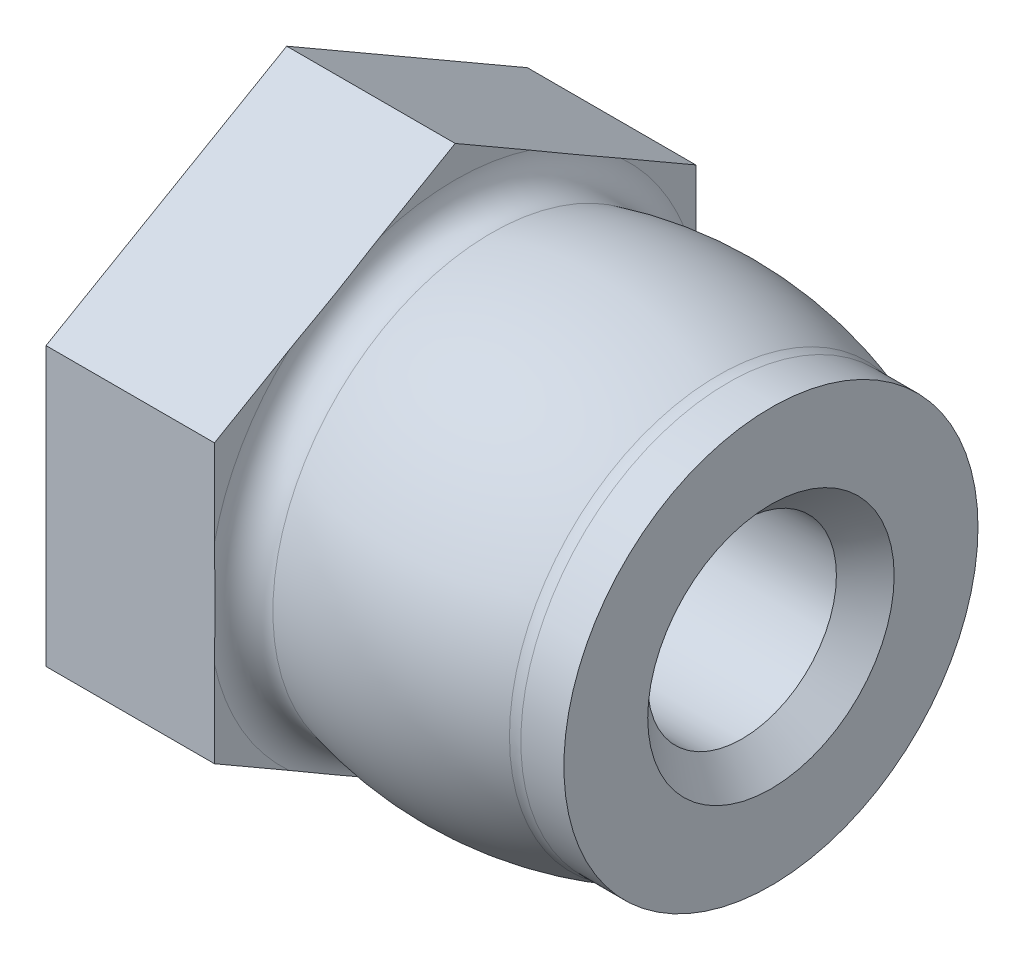
SolidWorks part; units mm, degrees
ref_plane "Front Plane" through (0, 0, 0) normal (0, 0, 1) x (1, 0, 0)
ref_plane "Top Plane" through (0, 0, 0) normal (0, 1, 0) x (1, 0, 0)
ref_plane "Right Plane" through (0, 0, 0) normal (1, 0, 0) x (0, 0, -1)
sketch "Sketch1" plane through (0, 0, 0) normal (0, 0, 1) x (1, 0, 0)
  line L0 (-40.9301, 0) -> (2005.574, 0) construction
  line L1 (0, -40.9301) -> (0, 2005.574) construction
  line L2 (0, 2.7314) -> (0, 1.2446)
  line L3 (0, 1.2446) -> (-5.7531, 1.2446)
  line L4 (-5.7531, 1.2446) -> (-5.7531, 3.175)
  line L5 (-5.7531, 3.175) -> (-3.5306, 3.175)
  line L6 (-3.5306, 3.175) -> (-3.5306, 2.7314)
  arc A0 (-3.5306, 2.7314) -> (0, 2.7314) centre (-1.7653, -2.032) cw
  dimension "D6" = 5.08
  dimension "D1" = 6.35
  dimension "D2" = 2.4892
  dimension "D3" = 2.2225
  dimension "D4" = 3.9878
  dimension "D5" = 5.4628
revolve "Revolve1" add sketch "Sketch1" angle 360 about L0
sketch "Sketch2" plane through (-5.7531, 0, 0) normal (-1, 0, 0) x (0, 0, 1)
  line L1 (0, 3.6662) -> (-3.175, 1.8331)
  line L2 (-3.175, 1.8331) -> (-3.175, -1.8331)
  line L3 (-3.175, -1.8331) -> (0, -3.6662)
  line L4 (0, -3.6662) -> (3.175, -1.8331)
  line L5 (3.175, -1.8331) -> (3.175, 1.8331)
  line L6 (3.175, 1.8331) -> (0, 3.6662)
  circle A0 centre (0, 0) radius 3.175 construction
  circle A1 centre (0, 0) radius 3.175 construction
  circle A2 centre (0, 0) radius 3.175
  circle M8 centre (0, 0) radius 1.2446
  circle M9 centre (0, 0) radius 3.175
extrude "Boss-Extrude1" add sketch "Sketch2" against normal up to surface (2.2225 mm away) contours L6 L1 M9 | L1 L2 M9 | L2 L3 M9 | L3 L4 M9 | L4 L5 M9 | L5 L6 M9 | M9 M8 region at (-5.7531, 3.2816, 0) region at (-5.7531, 1.6408, -2.8419) region at (-5.7531, 3.0852, 0) region at (-5.7531, 1.6408, 2.8419) region at (-5.7531, -1.6408, -2.8419) region at (-5.7531, -1.6408, 2.8419) region at (-5.7531, -3.2816, 0) up to face at (-3.5306, 0, 3.175)
sketch "Sketch3" plane through (0, 0, 0) normal (1, 0, 0) x (0, 0, -1)
  circle A0 centre (0, 0) radius 1.2446
  circle A1 centre (0, 0) radius 2.7314
  circle A2 centre (0, 0) radius 2.7314
  circle A3 centre (0, 0) radius 1.2446
extrude "Boss-Extrude2" add sketch "Sketch3" along normal blind 0.635
fillet "Fillet1" radius 0.381 1 edges at (-3.5306, 0, 2.7314) type face fillet first side face at (-3.5306, 0, 0) second side face at (-3.5306, 0, 2.7314)
fillet "Fillet2" radius 0.381 1 edges at (0, 0, -2.7314)
chamfer "Chamfer1" distance 0.381 1 edges at (0.635, 0, -1.2446)
